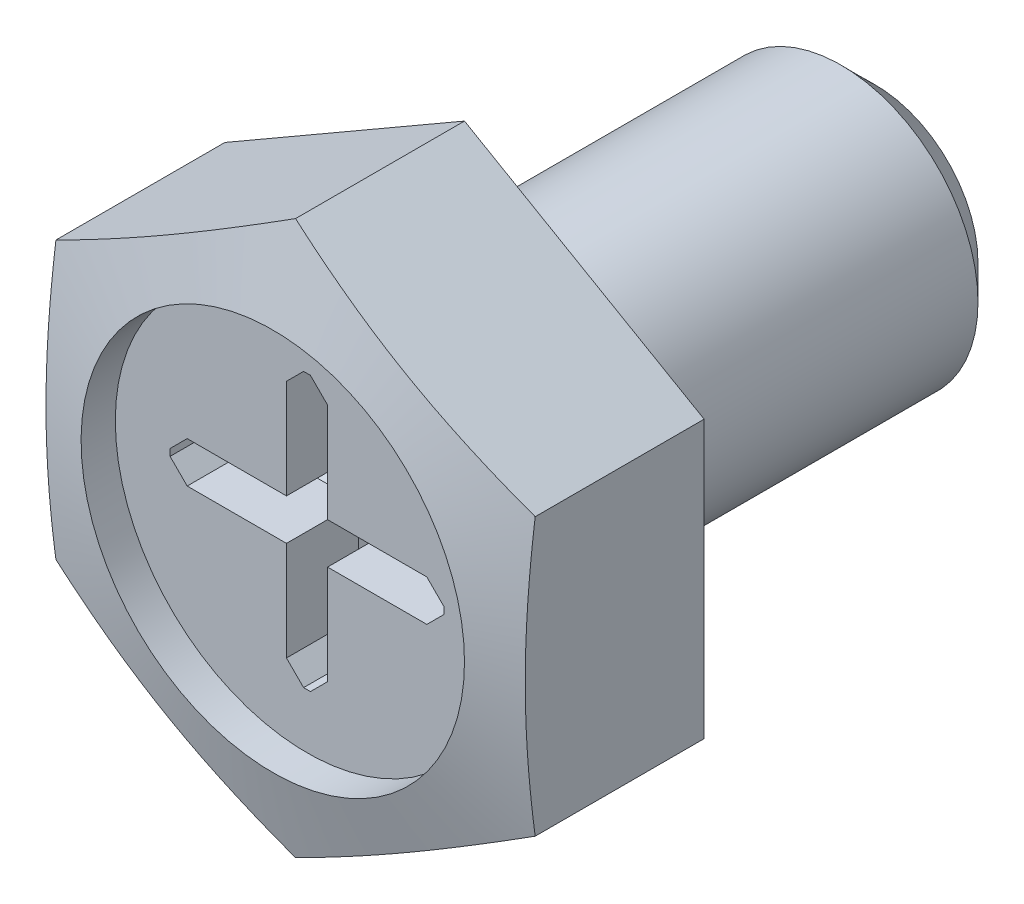
SolidWorks part; units mm, degrees
ref_plane "前视基准面" through (0, 0, 0) normal (0, 0, 1) x (1, 0, 0)
ref_plane "上视基准面" through (0, 0, 0) normal (0, 1, 0) x (1, 0, 0)
ref_plane "右视基准面" through (0, 0, 0) normal (1, 0, 0) x (0, 0, -1)
sketch "草图1" plane through (0, 0, 0) normal (0, 0, 1) x (1, 0, 0)
  line L1 (0, 4.0415) -> (-3.5, 2.0207)
  line L2 (-3.5, 2.0207) -> (-3.5, -2.0207)
  line L3 (-3.5, -2.0207) -> (0, -4.0415)
  line L4 (0, -4.0415) -> (3.5, -2.0207)
  line L5 (3.5, -2.0207) -> (3.5, 2.0207)
  line L6 (3.5, 2.0207) -> (0, 4.0415)
  circle A0 centre (0, 0) radius 3.5 construction
  dimension "s" = 7
extrude "凸台-拉伸1" add sketch "草图1" along normal blind 2.8
ref_axis "基准轴1" through (0, 0, 0) along (0, 0, -1)
sketch "草图3" plane through (0, 0, 0) normal (0, 0, 1) x (1, 0, 0)
  circle A0 centre (0, 0) radius 2
  dimension "d" = 4
extrude "凸台-拉伸3" add sketch "草图3" against normal blind 6
cosmetic thread "装饰螺纹线1" parameters "D2"=2.459
sketch "草图4" plane through (0, 0, 0) normal (1, 0, 0) x (0, 0, -1)
  line L0 (2.242, 0) -> (-1.4572, 0) construction
  line L2 (-2.8, 14) -> (-2.8, 2.8)
  line L3 (-2.8, 14) -> (0.201, 14)
  line L6 (-2.8, 2.0207) -> (-2.8, 4.0415) construction
  line L7 (-2.8, 2.8) -> (0.201, 14)
  dimension "D3" = 14
  dimension "D2" = 2.8
  dimension "D1" = 15
revolve "切除-旋转1" cut sketch "草图4" angle 360 about L0
sketch "草图7" plane through (0, 0, 2.8) normal (0, 0, 1) x (1, 0, 0)
  circle A0 centre (0, 0) radius 2.8
  circle A6 centre (0, 0) radius 2.8 construction
extrude "切除-拉伸3" cut sketch "草图7" against normal blind 0.5
sketch "草图6" plane through (0, 0, 2.3) normal (0, 0, 1) x (1, 0, 0)
  line L1 (2, 0.3) -> (-2, 0.3)
  line L2 (2, 0.3) -> (2, -0.3)
  line L3 (2, -0.3) -> (-2, -0.3)
  line L4 (-2, 0.3) -> (-2, -0.3)
  line L5 (0, -0.3) -> (0, 0.3) construction
  line L6 (2, 0) -> (-2, 0) construction
  line L7 (0.3, 2) -> (-0.3, 2)
  line L8 (0.3, 2) -> (0.3, -2)
  line L9 (0.3, -2) -> (-0.3, -2)
  line L10 (-0.3, 2) -> (-0.3, -2)
  line L11 (0, -2) -> (0, 2) construction
  line L12 (0.3, 0) -> (-0.3, 0) construction
  circle A2 centre (0, 0) radius 2.8 construction
  point P0 (0, 0)
  point P4 (0, 0)
  dimension "D1" = 0.6
  dimension "D2" = 0.8
extrude "切除-拉伸1" cut sketch "草图6" against normal offset from surface (1.3 mm away) 1 contours L10 L9 L8 L7 | L3 L4 L1 L2 up to face at (2, 0, 0)
chamfer "倒角1" distance 0.5 angle 45 1 edges at (2, 0, -6)
fillet "圆角1" radius 0.1 1 edges at (2, 0, 0)
ref_plane "基准面1" through (0, 0, 0) normal (0, 0, -1) x (-1, 0, 0)
chamfer "倒角2" distance 0.25 angle 45 12 edges at (1.15, 0.3, 1) (2, 0, 1) (1.15, -0.3, 1) (0.3, -1.15, 1) (0, -2, 1) (-0.3, -1.15, 1) (-1.15, -0.3, 1) (-2, 0, 1) (-1.15, 0.3, 1) (-0.3, 1.15, 1) (0, 2, 1) (0.3, 1.15, 1)
chamfer "倒角3" distance 0.25 angle 45 8 edges at (-2, 0.3, 1.775) (-2, -0.3, 1.775) (0.3, -2, 1.775) (-0.3, -2, 1.775) (2, -0.3, 1.775) (2, 0.3, 1.775) (0.3, 2, 1.775) (-0.3, 2, 1.775)
equation "\"D2@草图4\"=\"s@草图1\" * 0.4"
equation "\"D3@草图4\"=\"s@草图1\" * 2"
equation "\"D1@倒角1\"=\"d@草图3\" / 8"
